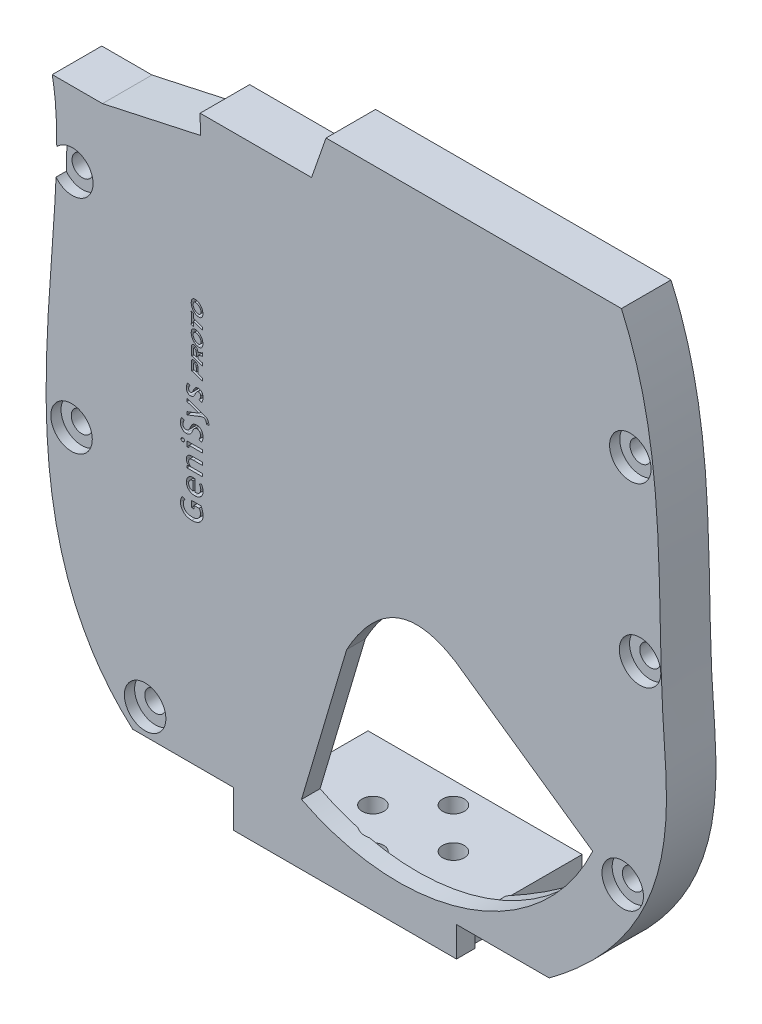
SolidWorks part; units mm, degrees
ref_plane "Front Plane" through (0, 0, 0) normal (0, 0, 1) x (1, 0, 0)
ref_plane "Top Plane" through (0, 0, 0) normal (0, 1, 0) x (1, 0, 0)
ref_plane "Right Plane" through (0, 0, 0) normal (1, 0, 0) x (0, 0, -1)
sketch "Sketch2" plane through (0, 0, 0) normal (0, 0, 1) x (1, 0, 0)
  line L0 (-18, 0) -> (18, 0)
  line L1 (-18, 0) -> (-18, 6)
  line L2 (18, 4.8369) -> (18, 0)
  line L3 (35.71, 104.3369) -> (-3.08, 104.3369)
  line L4 (-3.08, 104.3369) -> (-5.4197, 97.6369)
  line L5 (-5.4197, 97.6369) -> (-23.4197, 97.6369)
  line L6 (-23.4197, 97.6369) -> (-23.3737, 94.5493)
  line L7 (-23.3737, 94.5493) -> (-39.2, 91.09)
  spline S0 degree 3 poles (-18, 6) (-53.1212, 16.9957) (-35.2084, 66.9995) (-39.2, 91.09) knots 0 0 0 0 1 1 1 1
  spline S1 degree 3 poles (18, 4.8369) (37.3806, 15.4098) (45.3229, 29.9302) (41.68, 63.651) (44.3193, 88.8574) (35.71, 104.3369) knots 0 0 0 0 0.323626 0.459678 1 1 1 1
  dimension "D1" = 18
  dimension "D2" = 18
  dimension "D3" = 6
  dimension "D4" = 10.5
  dimension "D5" = 34.2
  dimension "D6" = 40.39
  dimension "D7" = 29.82
  dimension "D8" = 17.22
  dimension "D9" = 52.46
  dimension "D10" = 21.2
  dimension "D11" = 17.71
  dimension "D12" = 25.6263
  dimension "D13" = 25.26
  dimension "D14" = 38.79
  dimension "D15" = 109.25
  dimension "D16" = 6.7
  dimension "D17" = 18
  dimension "D18" = 16.2
extrude "Boss-Extrude1" add sketch "Sketch2" along normal blind 3
sketch "Sketch19" plane through (0, 0, 3) normal (0, 0, 1) x (1, 0, 0)
  line L0 (-3.953, 101.8369) -> (36.9908, 101.8369) construction
  line L1 (35.71, 104.3369) -> (-3.08, 104.3369) construction
  line L2 (16.315, 104.3369) -> (16.315, 82.7196) construction
  line L3 (-3.08, 104.3369) -> (-5.4197, 97.6369) construction
  line L4 (-5.0007, 98.8369) -> (38.0408, 98.8369) construction
  line L5 (-14.4197, 97.6369) -> (-14.4197, 83.1876) construction
  line L6 (-5.4197, 97.6369) -> (-23.4197, 97.6369) construction
  line L7 (37.36, 95.8369) -> (-20.5798, 95.8369) construction
  line L8 (-20.5798, 92.8369) -> (-0.9479, 92.8369) construction
  line L9 (-31.2868, 92.8197) -> (-28.0838, 78.1656) construction
  line L10 (-28.0838, 78.1656) -> (-24.3728, 78.9768) construction
  line L11 (-39.2, 91.09) -> (-23.3737, 94.5493) construction
  line L12 (-38.8717, 88.6027) -> (-23.0453, 92.0621) construction
  line L13 (5.02, 104.3369) -> (5.02, 84.8333) construction
  line L14 (27.61, 104.3369) -> (27.61, 87.3525) construction
  circle A0 centre (-14.4197, 79.8369) radius 1.6
  circle A1 centre (-27.7933, 76.8369) radius 1.6
  circle A17 centre (5.02, 79.8369) radius 1.6
  circle A18 centre (27.61, 79.8369) radius 1.6
  circle A22 centre (0, 14.3798) radius 1.6
  spline S0 degree 3 poles (18, 4.8369) (37.3806, 15.4098) (45.3229, 29.9302) (41.68, 63.651) (44.3193, 88.8574) (35.71, 104.3369) knots 0 0 0 0 0.323626 0.459678 1 1 1 1 construction
  spline S1 degree 3 poles (-39.2, 91.09) (-35.2084, 66.9995) (-53.1212, 16.9957) (-18, 6) knots 0 0 0 0 1 1 1 1 construction
  dimension "D7" = 16
  dimension "D17" = 3.2
  dimension "D19" = 3.2
  dimension "D29" = 3.2
  dimension "D4" = 3.2
  dimension "D5" = 3.2
  dimension "D1" = 2.5
  dimension "D6" = 3
  dimension "D8" = 19
  dimension "D9" = 3
  dimension "D10" = 2.5
  dimension "D21" = 16
  dimension "D22" = 16
sketch "Sketch21" plane through (0, 0, 3) normal (0, 0, 1) x (1, 0, 0)
  line L0 (-23, 59.1398) -> (-23, 39.8159) construction
  line L1 (-23, 60.0135) -> (-23, 71.0135) construction
  text T0 "GeniSys\r\n" font "Trebuchet MS" height 3.5
  text T1 "PROTO" font "Copperplate Gothic Bold" height in points 9
sketch "Sketch22" plane through (0, 0, 0) normal (0, 0, -1) x (-1, 0, 0)
  line L0 (-35.71, 104.3369) -> (3.08, 104.3369) construction
  line L1 (-16.315, 104.3369) -> (-16.315, 92.093) construction
  line L2 (14.4197, 97.6369) -> (14.4197, 88.3883) construction
  line L3 (5.4197, 97.6369) -> (23.4197, 97.6369) construction
  line L4 (31.2868, 92.8197) -> (29.4837, 84.5701) construction
  line L5 (23.3737, 94.5493) -> (39.2, 91.09) construction
  line L6 (28.356, 93.4603) -> (26.6477, 85.6448)
  line L7 (26.6477, 85.6448) -> (23.7169, 86.2854)
  line L8 (23.7169, 86.2854) -> (25.4252, 94.1009)
  line L9 (25.4252, 94.1009) -> (28.356, 93.4603)
  line L10 (32.5093, 84.3636) -> (35.4401, 83.7229)
  line L11 (34.2176, 92.179) -> (32.5093, 84.3636)
  line L12 (37.1484, 91.5384) -> (34.2176, 92.179)
  line L13 (35.4401, 83.7229) -> (37.1484, 91.5384)
  line L14 (-22.5125, 96.3369) -> (-19.5125, 96.3369)
  line L15 (-25.5125, 104.3369) -> (-25.5125, 88.3883) construction
  line L16 (-7.1175, 104.3369) -> (-7.1175, 88.3883) construction
  line L17 (17.4197, 89.6369) -> (20.4197, 89.6369)
  line L18 (11.4197, 97.6369) -> (8.4197, 97.6369)
  line L19 (11.4197, 97.6369) -> (11.4197, 89.6369)
  line L20 (11.4197, 89.6369) -> (8.4197, 89.6369)
  line L21 (8.4197, 97.6369) -> (8.4197, 89.6369)
  line L22 (17.4197, 97.6369) -> (20.4197, 97.6369)
  line L23 (20.4197, 97.6369) -> (20.4197, 89.6369)
  line L24 (17.4197, 97.6369) -> (17.4197, 89.6369)
  line L25 (-22.5125, 104.3369) -> (-22.5125, 96.3369)
  line L26 (-10.1175, 104.3369) -> (-13.1175, 104.3369)
  line L27 (-10.1175, 104.3369) -> (-10.1175, 96.3369)
  line L28 (-10.1175, 96.3369) -> (-13.1175, 96.3369)
  line L29 (-13.1175, 104.3369) -> (-13.1175, 96.3369)
  line L30 (-28.5125, 104.3369) -> (-31.5125, 104.3369)
  line L31 (-28.5125, 104.3369) -> (-28.5125, 96.3369)
  line L32 (-28.5125, 96.3369) -> (-31.5125, 96.3369)
  line L33 (-31.5125, 104.3369) -> (-31.5125, 96.3369)
  line L34 (-19.5125, 104.3369) -> (-19.5125, 96.3369)
  line L35 (-22.5125, 104.3369) -> (-19.5125, 104.3369)
  line L36 (-4.1175, 96.3369) -> (-1.1175, 96.3369)
  line L37 (-4.1175, 104.3369) -> (-4.1175, 96.3369)
  line L38 (-1.1175, 104.3369) -> (-1.1175, 96.3369)
  line L39 (-4.1175, 104.3369) -> (-1.1175, 104.3369)
  dimension "D1" = 3
  dimension "D2" = 8
  dimension "D3" = 3
  dimension "D4" = 3
  dimension "D5" = 8
  dimension "D6" = 3
  dimension "D7" = 8
  dimension "D8" = 8
  dimension "D9" = 3
  dimension "D10" = 3
  dimension "D11" = 3
  dimension "D12" = 3
sketch "Sketch28" plane through (0, 0, 0) normal (0, 0, -1) x (-1, 0, 0)
  line L8 (39.1964, 91.0908) -> (47.3092, 91.0908)
  line L9 (39.2, 91.09) -> (23.3737, 94.5493) construction
  line L10 (-35.71, 104.3369) -> (-44.6454, 104.3369)
  line L11 (-18, 4.8369) -> (-32.9704, 4.8369)
  line L12 (18, 6) -> (34.3245, 6)
  line L16 (31.4704, 100.9684) -> (31.5401, 105.6369)
  line L17 (31.5401, 105.6369) -> (11.0998, 105.6369)
  line L18 (11.0998, 105.6369) -> (8.7601, 112.3369)
  line L19 (8.7601, 112.3369) -> (-40.4147, 112.3369)
  line L20 (-26, 0.2007) -> (-26, -8)
  line L21 (-26, -8) -> (26, -8)
  line L22 (26, -8) -> (26, 0.5564)
  line L23 (48.3351, 97.2821) -> (31.4704, 100.9684)
  line L37 (23.3737, 94.5493) -> (23.4197, 97.6369)
  line L38 (23.4197, 97.6369) -> (5.4197, 97.6369)
  line L39 (5.4197, 97.6369) -> (3.08, 104.3369)
  line L40 (3.08, 104.3369) -> (-35.71, 104.3369)
  line L41 (-18, 4.8369) -> (-18, 0)
  line L42 (-18, 0) -> (18, 0)
  line L43 (18, 0) -> (18, 6)
  line L44 (39.2, 91.09) -> (23.3737, 94.5493)
  line L45 (23.3737, 94.5493) -> (23.4197, 97.6369)
  line L52 (39.2, 91.09) -> (39.1964, 91.0908)
  spline S4 degree 3 poles (1417.7386, 2734.1164) (931.0609, 1859.0634) (444.3833, 984.0104) (-42.6075, 108.3942) (-42.9227, 107.8318) (-43.5223, 106.6945) (-43.8102, 106.1212) (-45.1935, 103.2322) (-46.1189, 100.849) (-47.2785, 97.1832) (-47.6269, 95.9461) (-48.2547, 93.4444) (-48.5346, 92.1773) (-49.2787, 88.3586) (-49.6462, 85.8005) (-50.4828, 78.101) (-50.6866, 72.9333) (-50.878, 65.1741) (-50.9223, 62.5873) (-51.0428, 57.4143) (-51.1187, 54.8281) (-51.3182, 50.9505) (-51.4034, 49.6583) (-51.586, 47.0742) (-51.6802, 45.7822) (-51.9069, 41.9051) (-51.9817, 39.3189) (-51.7684, 35.4333) (-51.6426, 34.1353) (-51.2608, 31.5439) (-51.0076, 30.2681) (-50.0524, 26.5034) (-49.1542, 24.0772) (-47.6934, 21.1525) (-47.3842, 20.573) (-46.7402, 19.4376) (-46.4044, 18.8801) (-45.358, 17.2364) (-44.6084, 16.1791) (-43.0152, 14.134) (-42.1717, 13.1462) (-40.8431, 11.7112) (-40.3889, 11.2399) (-39.4646, 10.3162) (-38.995, 9.8642) (-36.6124, 7.6489) (-34.597, 6.0193) (70.4946, -70.5483) (365.9066, 105.7005) (-1528.4755, -2577.8805) knots -24.243764 -24.243764 -24.243764 -24.243764 0.03125 0.03125 0.046875 0.046875 0.0625 0.0625 0.125 0.125 0.15625 0.15625 0.1875 0.1875 0.25 0.25 0.375 0.375 0.4375 0.4375 0.5 0.5 0.53125 0.53125 0.5625 0.5625 0.625 0.625 0.65625 0.65625 0.6875 0.6875 0.75 0.75 0.765625 0.765625 0.78125 0.78125 0.8125 0.8125 0.84375 0.84375 0.859375 0.859375 0.875 0.875 0.9375 0.9375 4.010814 4.010814 4.010814 4.010814 only from (-40.4147, 112.3369) to (-26, 0.2007)
  spline S5 degree 3 poles (1275.9194, -2677.6257) (-1003.8484, 864.793) (-110.9498, -98.408) (32.5557, 4.5293) (33.4143, 5.2074) (34.6569, 6.2891) (35.0635, 6.6604) (35.8613, 7.4251) (36.2533, 7.8194) (38.1543, 9.8259) (39.4989, 11.5534) (41.2764, 14.3107) (41.8289, 15.2575) (42.8576, 17.2041) (43.3351, 18.2078) (44.6383, 21.2447) (45.3428, 23.3148) (46.4936, 27.5266) (46.9396, 29.6683) (47.4556, 32.9232) (47.6022, 34.0173) (47.8487, 36.2037) (47.9488, 37.2967) (48.19, 40.5756) (48.2724, 42.7612) (48.3506, 49.317) (48.1788, 53.6865) (47.6643, 62.4247) (47.3159, 66.7938) (46.8816, 73.346) (46.7519, 75.5296) (46.5845, 79.8942) (46.5444, 82.0752) (46.6417, 85.3422) (46.7008, 86.4304) (46.8549, 88.0608) (46.9173, 88.6039) (47.0719, 89.6894) (47.1668, 90.2316) (211.0779, 1079.4881) (374.8991, 2068.2022) (538.7204, 3056.9163) knots -4.957742 -4.957742 -4.957742 -4.957742 0.0625 0.0625 0.09375 0.09375 0.109375 0.109375 0.125 0.125 0.1875 0.1875 0.21875 0.21875 0.25 0.25 0.3125 0.3125 0.375 0.375 0.40625 0.40625 0.4375 0.4375 0.5 0.5 0.625 0.625 0.75 0.75 0.8125 0.8125 0.875 0.875 0.90625 0.90625 0.921875 0.921875 0.9375 0.9375 29.42208 29.42208 29.42208 29.42208 only from (26, 0.5564) to (48.3351, 97.2821)
  spline S6 degree 3 poles (-44.6454, 104.3369) (-45.5093, 102.4054) (-46.2527, 100.426) (-47.2785, 97.1832) (-47.6269, 95.9461) (-48.2547, 93.4444) (-48.5346, 92.1773) (-49.2787, 88.3586) (-49.6462, 85.8005) (-50.4828, 78.101) (-50.6866, 72.9333) (-50.878, 65.1741) (-50.9223, 62.5873) (-51.0428, 57.4143) (-51.1187, 54.8281) (-51.3182, 50.9505) (-51.4034, 49.6583) (-51.586, 47.0742) (-51.6802, 45.7822) (-51.9069, 41.9051) (-51.9817, 39.3189) (-51.7684, 35.4333) (-51.6426, 34.1353) (-51.2608, 31.5439) (-51.0076, 30.2681) (-50.0524, 26.5034) (-49.1542, 24.0772) (-47.6934, 21.1525) (-47.3842, 20.573) (-46.7402, 19.4376) (-46.4044, 18.8801) (-45.358, 17.2364) (-44.6084, 16.1791) (-43.0152, 14.134) (-42.1717, 13.1462) (-40.8431, 11.7112) (-40.3889, 11.2399) (-39.4646, 10.3162) (-38.995, 9.8642) (-36.7547, 7.7813) (-34.8974, 6.2635) (-32.9704, 4.8369) knots 0.073318 0.073318 0.073318 0.073318 0.125 0.125 0.15625 0.15625 0.1875 0.1875 0.25 0.25 0.375 0.375 0.4375 0.4375 0.5 0.5 0.53125 0.53125 0.5625 0.5625 0.625 0.625 0.65625 0.65625 0.6875 0.6875 0.75 0.75 0.765625 0.765625 0.78125 0.78125 0.8125 0.8125 0.84375 0.84375 0.859375 0.859375 0.875 0.875 0.932833 0.932833 0.932833 0.932833
  spline S7 degree 3 poles (34.3245, 6) (34.7105, 6.3381) (35.0898, 6.6856) (35.8613, 7.4251) (36.2533, 7.8194) (38.1543, 9.8259) (39.4989, 11.5534) (41.2764, 14.3107) (41.8289, 15.2575) (42.8576, 17.2041) (43.3351, 18.2078) (44.6383, 21.2447) (45.3428, 23.3148) (46.4936, 27.5266) (46.9396, 29.6683) (47.4556, 32.9232) (47.6022, 34.0173) (47.8487, 36.2037) (47.9488, 37.2967) (48.19, 40.5756) (48.2724, 42.7612) (48.3506, 49.317) (48.1788, 53.6865) (47.6643, 62.4247) (47.3159, 66.7938) (46.8816, 73.346) (46.7519, 75.5296) (46.5845, 79.8942) (46.5444, 82.0752) (46.6417, 85.3422) (46.7008, 86.4304) (46.8549, 88.0608) (46.9173, 88.6039) (47.0719, 89.6894) (47.1668, 90.2316) (47.2742, 90.8795) (47.2917, 90.9852) (47.3092, 91.0908) knots 0.09478 0.09478 0.09478 0.09478 0.109375 0.109375 0.125 0.125 0.1875 0.1875 0.21875 0.21875 0.25 0.25 0.3125 0.3125 0.375 0.375 0.40625 0.40625 0.4375 0.4375 0.5 0.5 0.625 0.625 0.75 0.75 0.8125 0.8125 0.875 0.875 0.90625 0.90625 0.921875 0.921875 0.9375 0.9375 0.940543 0.940543 0.940543 0.940543
  spline S10 degree 3 poles (2802.2864, -849.4291) (-150.9539, 334.685) (-31.6191, 156.7782) (-51.7246, -29.3265) (163.8863, -81.282) (2961.8774, -332.2275) knots -2.761715 -2.761715 -2.761715 -2.761715 0.540322 0.676374 2.757275 2.757275 2.757275 2.757275 only from (-35.71, 104.3369) to (-18, 4.8369)
  spline S11 degree 3 poles (-2451.756, 1700.8507) (2495.8296, -2099.3521) (-2351.947, 2305.3779) (2338.0583, -1833.9237) knots -2.517704 -2.517704 -2.517704 -2.517704 3.848292 3.848292 3.848292 3.848292 only from (18, 6) to (39.2, 91.09)
  spline S12 degree 3 poles (-35.71, 104.3369) (-44.3193, 88.8574) (-41.68, 63.651) (-45.3229, 29.9302) (-37.3806, 15.4098) (-18, 4.8369) knots 0 0 0 0 0.540322 0.676374 1 1 1 1
  spline S13 degree 3 poles (18, 6) (53.1212, 16.9957) (35.2084, 66.9995) (39.2, 91.09) knots 0 0 0 0 1 1 1 1
  spline M15 degree 3 poles (-35.71, 104.3369) (-44.3193, 88.8574) (-41.68, 63.651) (-45.3229, 29.9302) (-37.3806, 15.4098) (-18, 4.8369) knots 0 0 0 0 0.540322 0.676374 1 1 1 1
  spline M19 degree 3 poles (18, 6) (53.1212, 16.9957) (35.2084, 66.9995) (39.2, 91.09) knots 0 0 0 0 1 1 1 1
  line M20 (39.2, 91.09) -> (23.3737, 94.5493)
  dimension "D1" = 8
  dimension "D2" = 0
extrude "Boss-Extrude4" add sketch "Sketch28" along normal blind 5 and the other way blind 3 contours L10 S6 L11 M15 | L12 S7 L8 M20 M19 region at (-41.2291, 46.2537, 0) region at (43.5345, 51.6185, 0)
sketch "Sketch29" plane through (0, 0, 0) normal (0, 0, -1) x (-1, 0, 0)
  line L0 (-35.71, 104.3369) -> (3.08, 104.3369)
  line L1 (3.08, 104.3369) -> (5.4197, 97.6369)
  line L2 (1.5667, 97.6369) -> (-38.7134, 97.6369)
  line L3 (-38.7134, 97.6369) -> (-38.7134, 104.3369)
  line L4 (5.4197, 97.6369) -> (23.4197, 97.6369)
  line L5 (23.4197, 97.6369) -> (23.3737, 94.5493)
  line L6 (23.3737, 94.5493) -> (39.1964, 91.0908)
  line L7 (38.6909, 86.3011) -> (39.7378, 91.0908)
  line L8 (38.6909, 86.3011) -> (22.3514, 89.8725)
  line L9 (22.3514, 89.8725) -> (5.4197, 89.8725)
  line L10 (-35.71, 104.3369) -> (-44.6454, 104.3369) construction
  line L11 (5.4197, 89.8725) -> (1.5667, 97.6369)
  line L12 (-38.7134, 104.3369) -> (-35.71, 104.3369)
  line L13 (39.1964, 91.0908) -> (47.3092, 91.0908) construction
  line L14 (39.7378, 91.0908) -> (39.1964, 91.0908)
  spline S0 degree 3 poles (-35.71, 104.3369) (-44.3193, 88.8574) (-41.68, 63.651) (-45.3229, 29.9302) (-37.3806, 15.4098) (-18, 4.8369) knots 0 0 0 0 0.540322 0.676374 1 1 1 1 construction
  spline S1 degree 3 poles (39.2, 91.09) (35.2084, 66.9995) (53.1212, 16.9957) (18, 6) knots 0 0 0 0 1 1 1 1 construction
extrude "Boss-Extrude7" add sketch "Sketch29" along normal blind 5
extrude "Cut-Extrude3" cut sketch "Sketch21" against normal blind 2
sketch "Sketch30" plane through (0, 0, 3) normal (0, 0, 1) x (1, 0, 0)
  line L0 (-18, 0) -> (18, 0) construction
  line L1 (17.8718, 41.5075) -> (40.0011, 26.0823)
  line L3 (25.5125, 104.3369) -> (25.5125, 88.3883) construction
  line L4 (0.2543, 34.429) -> (-7.0409, 9.8148)
  arc A0 (-7.0409, 9.8148) -> (40.0011, 26.0823) centre (8.6247, 40.6646) ccw
  spline S1 degree 2 poles (17.8718, 41.5075) (7.6643, 47.8845) (0.2543, 34.429) knots 0 0 0 1 1 1
  point P6 (15.5125, 30)
  dimension "D2" = 30
  dimension "D3" = 10
extrude "Cut-Extrude4" cut sketch "Sketch30" against normal blind 10 contours L1 S1 L4 A0 region at (14.619, 23.2827, 3)
sketch "Sketch31" plane through (0, 0, 0) normal (0, 0, -1) x (-1, 0, 0)
  line L1 (-18, 4.8369) -> (18, 4.8369)
  line L2 (-18, 4.8369) -> (-18, 0)
  line L3 (-18, 0) -> (18, 0)
  line L4 (18, 4.8369) -> (18, 0)
sketch "Sketch32" plane through (0, 0, 0) normal (0, 0, -1) x (-1, 0, 0)
  line L1 (-17.3, 3.7866) -> (17.3, 3.7866)
  line L3 (-17.3, 0) -> (17.3, 0)
  line L5 (-17.3, 3.7866) -> (-17.3, 0)
  line L6 (17.3, 3.7866) -> (17.3, 0.2665)
  line L7 (17.3, 0.2665) -> (17.3, 0)
extrude "Boss-Extrude10" add sketch "Sketch32" along normal blind 18
sketch "Sketch33" plane through (0, 0, 0) normal (0, -1, 0) x (1, 0, 0)
  line L0 (37.36, 3) -> (-20.5798, 3) construction
  circle A0 centre (0, -8) radius 6.5 construction
  circle A1 centre (0, -1.5) radius 1.75
  circle A2 centre (6.5, -8) radius 1.75
  circle A3 centre (0, -14.5) radius 1.75
  circle A4 centre (-6.5, -8) radius 1.75
  point P15 (0, -8)
  dimension "D1" = 13
  dimension "D3" = 4
  dimension "D4" = 3.5
  dimension "D2" = 11
extrude "Cut-Extrude5" cut sketch "Sketch33" against normal blind 10
hole_wizard "CBORE for M3 SBHCS1" positions "Sketch34" profile "Sketch35" counterbore size "M3" standard "ANSI Metric" end condition through all
sketch "Sketch34" plane through (60.806, 52.278, 3) normal (0, 0, 1) x (1, 0, 0)
  point P0 (-104.8732, 26.862)
  point P1 (-14.7294, 31.9842)
  point P2 (-13.1539, 4.198)
  point P3 (-15.9572, -28.4297)
  point P4 (-93.1113, -42.1412)
  point P5 (-104.998, -8.999)
sketch "Sketch35" plane through (-44.0672, 79.14, 3) normal (1, 0, 0) x (0, -1, 0)
  line L0 (0, 0) -> (0, 21)
  line L1 (0, 21) -> (1.7, 21)
  line L2 (1.7, 21) -> (1.7, 1.65)
  line L3 (1.7, 1.65) -> (3.35, 1.65)
  line L4 (3.35, 1.65) -> (3.35, 0)
  line L5 (3.35, 0) -> (0, 0)
  line L6 (0, -6.35) -> (0, 107.95) construction
  dimension "Thru Hole Dia." = 3.4
  dimension "Thru Hole Depth" = 21
  dimension "C'Bore Dia." = 6.7
  dimension "C'Bore Depth" = 1.65
